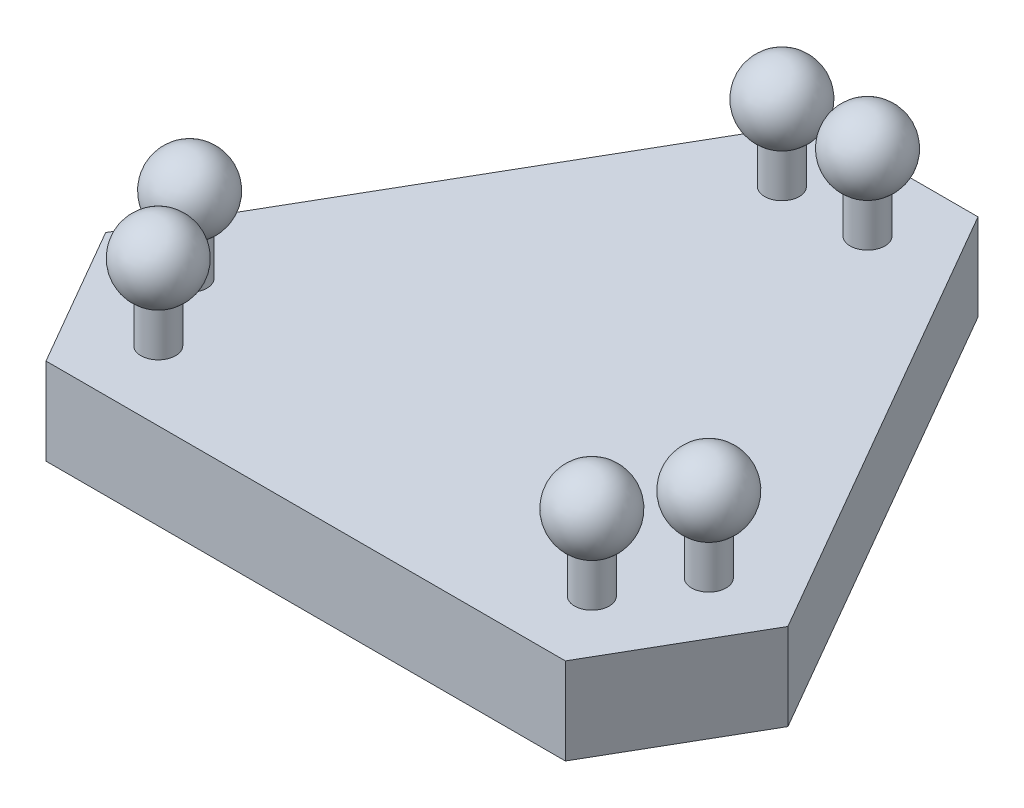
SolidWorks part; units mm, degrees
ref_plane "Front Plane" through (0, 0, 0) normal (0, 0, 1) x (1, 0, 0)
ref_plane "Top Plane" through (0, 0, 0) normal (0, 1, 0) x (1, 0, 0)
ref_plane "Right Plane" through (0, 0, 0) normal (1, 0, 0) x (0, 0, -1)
sketch "Sketch1" plane through (0, 0, 0) normal (0, 1, 0) x (1, 0, 0)
  line L0 (0, 0) -> (0, 40) construction
  line L1 (-9.3918, 40) -> (-39.3369, -11.8664)
  line L2 (-29.9451, -28.1336) -> (29.9451, -28.1336)
  line L3 (39.3369, -11.8664) -> (9.3918, 40)
  line L4 (-9.3918, 40) -> (9.3918, 40)
  line L5 (39.3369, -11.8664) -> (29.9451, -28.1336)
  line L6 (-29.9451, -28.1336) -> (-39.3369, -11.8664)
  circle A1 centre (0, 0) radius 28.1336 construction
  point P16 (0, 0)
  dimension "D1" = 40
extrude "Boss-Extrude1" add sketch "Sketch1" along normal blind 10
sketch "Sketch2" plane through (0, 0, 0) normal (0, 0, 1) x (1, 0, 0)
  line L0 (-0.3013, -20) -> (-15, 0)
  line L2 (0, 0) -> (0, -20)
  line L5 (0, -20) -> (-0.3013, -20)
  line L6 (-15, 0) -> (0, 0)
  dimension "D1" = 20
  dimension "D3" = 15
revolve "Revolve1" add sketch "Sketch2" angle 360 about L2
sketch "Sketch3" plane through (0, 10, 0) normal (0, 1, 0) x (1, 0, 0)
  line L0 (-17.4362, 10.0668) -> (-24.3644, 14.0668) construction
  line L1 (-9.3918, 40) -> (-39.3369, -11.8664) construction
  line L2 (-24.3644, 14.0668) -> (-17.4362, 10.0668) construction
  line L3 (-17.4362, 10.0668) -> (-4.9362, 31.7174) construction
  line L4 (-4.9362, 31.7174) -> (-29.9362, -11.5839) construction
  circle A1 centre (-17.4362, 10.0668) radius 25 construction
  circle A3 centre (-4.9362, 31.7174) radius 2
  circle A4 centre (-29.9362, -11.5839) radius 2
  circle A5 centre (4.9362, 31.7174) radius 2
  circle A6 centre (29.9362, -11.5839) radius 2
  circle A7 centre (25, -20.1336) radius 2
  circle A8 centre (-25, -20.1336) radius 2
  point P19 (0, 0)
  dimension "D1" = 8
  dimension "D2" = 3
extrude "Boss-Extrude2" add sketch "Sketch3" along normal blind 5
dome "Dome1" faces to dome 1 distance 8 reverse direction no elliptical dome no face at (-29.9362, 15, 13.5839) parameters "D1"=8
dome "Dome2" faces to dome 1 distance 8 reverse direction no elliptical dome no face at (-4.9362, 15, -29.7174) parameters "D1"=8
dome "Dome3" faces to dome 1 distance 8 reverse direction no elliptical dome no face at (4.9362, 15, -29.7174) parameters "D1"=8
dome "Dome4" faces to dome 1 distance 8 reverse direction no elliptical dome no face at (29.9362, 15, 13.5839) parameters "D1"=8
dome "Dome5" faces to dome 1 distance 8 reverse direction no elliptical dome no face at (25, 15, 22.1336) parameters "D1"=8
dome "Dome6" faces to dome 1 distance 8 reverse direction no elliptical dome no face at (-25, 15, 22.1336) parameters "D1"=8
